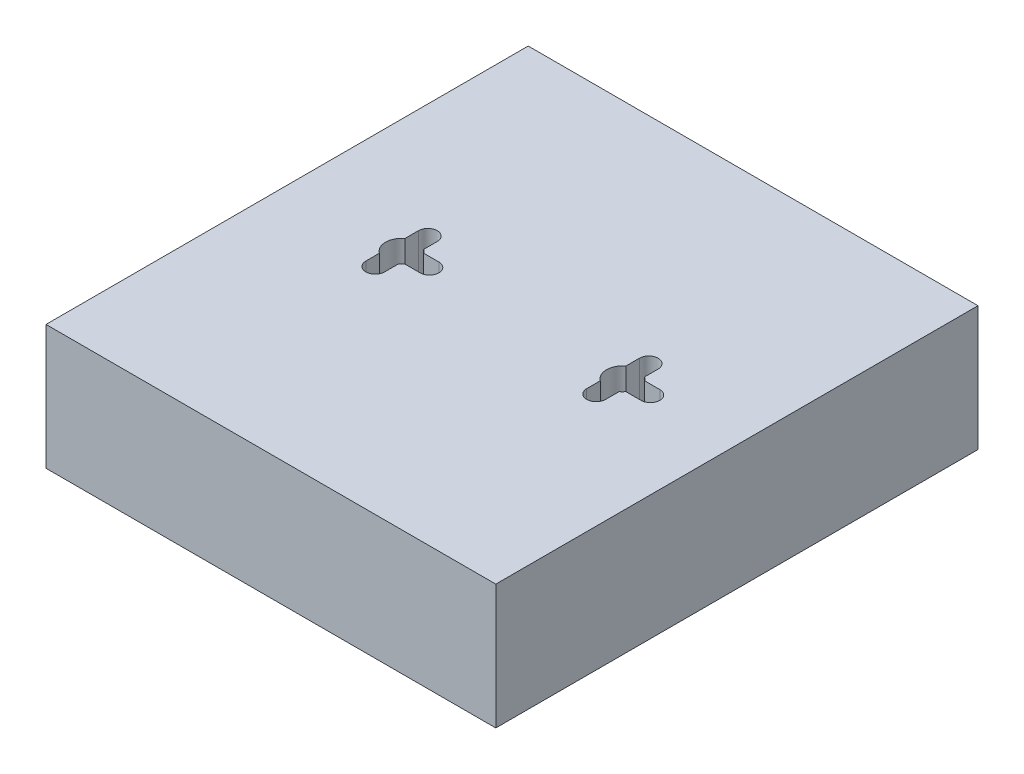
SolidWorks part; units mm, degrees
ref_plane "Front Plane" through (0, 0, 0) normal (0, 0, 1) x (1, 0, 0)
ref_plane "Top Plane" through (0, 0, 0) normal (0, 1, 0) x (1, 0, 0)
ref_plane "Right Plane" through (0, 0, 0) normal (1, 0, 0) x (0, 0, -1)
sketch "Sketch1" plane through (0, 0, 0) normal (0, 1, 0) x (1, 0, 0)
  line L0 (70.2401, 56.0118) -> (70.2401, 44.9882) construction
  line L1 (0, 0) -> (94.2086, 0)
  line L2 (0, 0) -> (0, 101)
  line L3 (0, 101) -> (94.2086, 101)
  line L4 (94.2086, 0) -> (94.2086, 101)
  line L5 (72.2086, 56.0118) -> (72.2086, 44.9882)
  line L6 (68.2716, 56.0118) -> (68.2716, 44.9882)
  line L7 (70.2401, 50.5) -> (76.0948, 50.5) construction
  line L8 (70.2401, 52.4685) -> (76.0948, 52.4685)
  line L9 (70.2401, 48.5315) -> (76.0948, 48.5315)
  line L10 (70.2401, 50.5) -> (66.9127, 50.5) construction
  line L11 (0, 50.5) -> (94.2086, 50.5) construction
  line L12 (47.1043, 0) -> (47.1043, 101) construction
  line L13 (23.9685, 56.0118) -> (23.9685, 44.9882) construction
  line L14 (25.937, 56.0118) -> (25.937, 44.9882)
  line L15 (22, 56.0118) -> (22, 44.9882)
  line L16 (23.9685, 50.5) -> (29.8232, 50.5) construction
  line L17 (23.9685, 52.4685) -> (29.8232, 52.4685)
  line L18 (23.9685, 48.5315) -> (29.8232, 48.5315)
  line L19 (23.9685, 50.5) -> (20.6411, 50.5) construction
  circle A0 centre (70.2401, 50.5) radius 3.3274
  arc A1 (72.2086, 56.0118) -> (68.2716, 56.0118) centre (70.2401, 56.0118) ccw
  arc A2 (68.2716, 44.9882) -> (72.2086, 44.9882) centre (70.2401, 44.9882) ccw
  arc A3 (70.2401, 52.4685) -> (70.2401, 48.5315) centre (70.2401, 50.5) ccw
  arc A4 (76.0948, 48.5315) -> (76.0948, 52.4685) centre (76.0948, 50.5) ccw
  circle A5 centre (23.9685, 50.5) radius 3.3274
  arc A6 (25.937, 56.0118) -> (22, 56.0118) centre (23.9685, 56.0118) ccw
  arc A7 (22, 44.9882) -> (25.937, 44.9882) centre (23.9685, 44.9882) ccw
  arc A8 (23.9685, 52.4685) -> (23.9685, 48.5315) centre (23.9685, 50.5) ccw
  arc A9 (29.8232, 48.5315) -> (29.8232, 52.4685) centre (29.8232, 50.5) ccw
  point P9 (70.2401, 50.5)
  point P14 (73.1675, 50.5)
  point P20 (70.2401, 43.0197)
  point P21 (70.2401, 57.9803)
  point P27 (78.0633, 50.5)
  point P29 (73.4222, 51.177)
  point P30 (0, 0)
  point P35 (23.9685, 50.5)
  point P40 (26.8959, 50.5)
  point P46 (23.9685, 43.0197)
  point P47 (23.9685, 57.9803)
  point P50 (31.7917, 50.5)
  point P51 (0, 0)
  dimension "D6" = 6.6548
  dimension "D11" = 6.6548
  dimension "D1" = 94.2086
  dimension "D2" = 101
  dimension "D3" = 14.9606
  dimension "D4" = 11.1506
  dimension "D5" = 3.937
  dimension "D7" = 22
  dimension "D8" = 14.9606
  dimension "D9" = 3.937
  dimension "D10" = 11.1506
  dimension "D12" = 22
extrude "Boss-Extrude1" add sketch "Sketch1" along normal blind 26.1 contours L1 L4 L3 L2 A9 L18 A5 L14 A7 L15 A6 L17 A4 L9 A0 L5 A2 L6 A1 L8 region at (47.0853, 0, -50.5)
sketch "Sketch2" plane through (0, 0, 0) normal (0, -1, 0) x (1, 0, 0)
  line L0 (0, 0) -> (94.2086, 0) construction
  line L1 (11.938, -20.32) -> (82.2706, -20.32) construction
  line L2 (11.938, -20.32) -> (11.938, -85.76) construction
  line L3 (11.938, -85.76) -> (82.2706, -85.76) construction
  line L4 (82.2706, -20.32) -> (82.2706, -85.76) construction
  line L5 (0, -101) -> (94.2086, -101) construction
  line L6 (94.2086, 0) -> (94.2086, -101) construction
  line L7 (0, 0) -> (0, -101) construction
  circle A0 centre (11.938, -20.32) radius 5.461
  circle A1 centre (82.2706, -20.32) radius 5.461
  circle A2 centre (11.938, -85.76) radius 5.461
  circle A3 centre (82.2706, -85.76) radius 5.461
  dimension "D5" = 10.922
  dimension "D1" = 20.32
  dimension "D2" = 15.24
  dimension "D3" = 11.938
  dimension "D4" = 11.938
extrude "Boss-Extrude2" add sketch "Sketch2" along normal blind 2.54
equation "\"D4@Sketch2\"=\"D3@Sketch2\""
